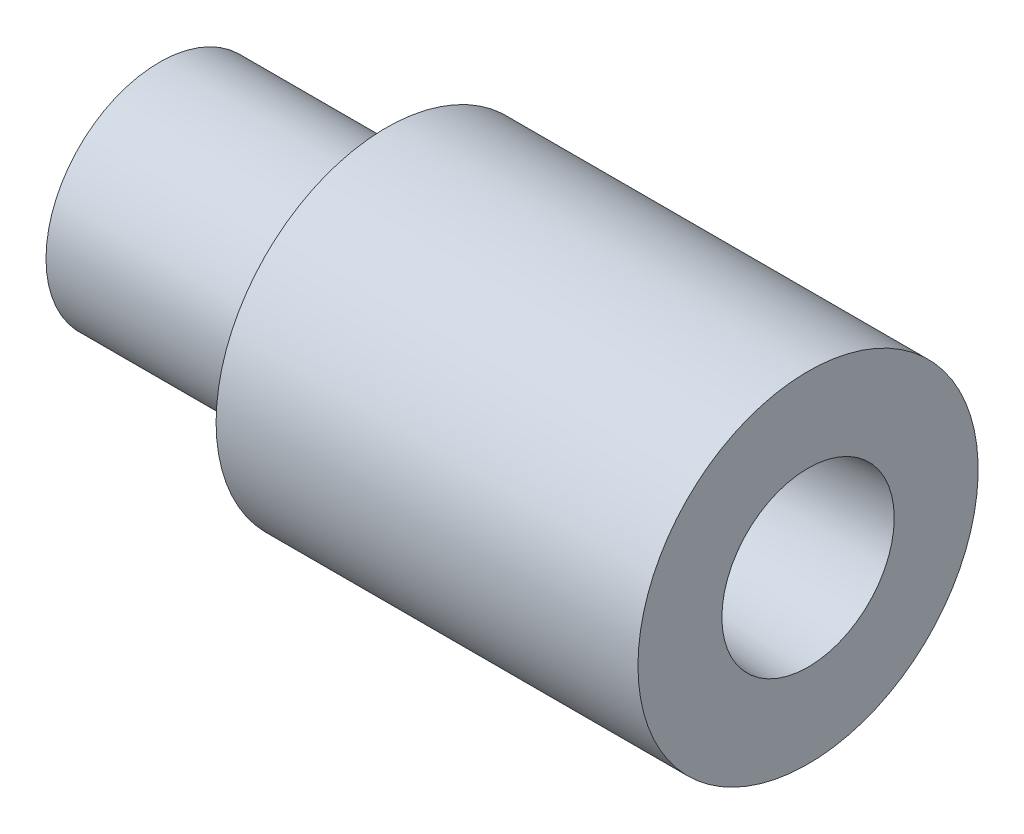
SolidWorks part; units mm, degrees
ref_plane "Front Plane" through (0, 0, 0) normal (0, 0, 1) x (1, 0, 0)
ref_plane "Top Plane" through (0, 0, 0) normal (0, 1, 0) x (1, 0, 0)
ref_plane "Right Plane" through (0, 0, 0) normal (1, 0, 0) x (0, 0, -1)
sketch "Sketch1" plane through (0, 0, 0) normal (0, 1, 0) x (1, 0, 0)
  line L0 (0, 0) -> (0, 2.286) construction
  line L1 (0, 2.286) -> (0, 6.35)
  line L2 (12.7, 9.525) -> (36.3237, 9.525)
  line L3 (36.3237, 9.525) -> (36.3237, 4.826)
  line L4 (36.3237, 4.826) -> (0, 2.286)
  line L5 (0, 0) -> (36.3237, 0) construction
  line L6 (36.3237, 0) -> (36.3237, 4.826) construction
  line L8 (12.7, 6.35) -> (12.7, 9.525)
  line L12 (0, 6.35) -> (12.7, 6.35)
  dimension "D1" = 2.286
  dimension "D2" = 4.826
  dimension "D3" = 4
  dimension "D4" = 9.525
  dimension "D5" = 6.35
  dimension "D6" = 12.7
revolve "Revolve1" add sketch "Sketch1" angle 360 about L5
equation "\"z\" = 8\t\t\t\t'number of blades"
equation "\"de\" = 0.43in\t\t\t'entrance eye diameter"
equation "\"de_length\" = 10mm\t\t'entrance eye consistent length"
equation "\"d_exit\" = 0.18in \t\t'throat aka d1"
equation "\"d2\" = 2.1in \t\t\t'outer diameter of the impeller"
equation "\"b2\" = .2in\t\t\t'tip height from disc surface at d2; slightly higher than d_exit"
equation "\"b1\" = \"b2\" + (\"d2\"/2 - \"de\"/2)*tan(\"theta\") \t\t\t'tip height from disc surface at inlet eye"
equation "\"theta\" = 12\t\t\t'angle of blades from inner to outer "
equation "\"ae\" = 3.14*(\"de\"^2)/4\t\t'entrance eye area'"
equation "\"ce\" = 3.14*\"de\"\t\t'entrance eye circumference"
equation "\"av_ratio\" = .325\t\t'ratio of av/ae at N_s of 470, range is .275 to .375, .325 ideal. High ratio means bigger area means smaller blades"
equation "\"av\" = \"ae\"*\"av_ratio\"\t\t'area between just two blades"
equation "\"s_open\" = \"av\"/\"b1\"\t\t'width of open area"
equation "\"s\"=\"ce\" - \"z\"*\"s_open\""
equation "\"min blade thickness\" = .15in"
equation "\"bearing OD\" = 30mm"
equation "\"bearing ID\"= 10mm"
equation "\"bearing depth\"= 9mm"
equation "\"bearing outer race thickness\"= 1mm"
equation "\"bearing inner race thickness\"= 1mm"
equation "\"bearing bore\" = \"bearing depth\" + 1mm"
equation "\"lower seal OD\" = .917in\t\t'this is https://www.mcmaster.com/#9281k121/=174001b"
equation "\"lower seal ID\"= .375in"
equation "\"lower seal depth\" = .625in + .218in"
equation "\"lower seal bore\" = \"lower seal depth\" + 1mm"
equation "\"upper seal OD\" = 1.125in\t'this is https://www.mcmaster.com/#5154t33/=173zuau, needs to be visually inspected before machining!"
equation "\"upper seal ID\"= 0.625in"
equation "\"upper seal depth\"= .25in\t'aka height; these values need to be confirmed by inspection!! We may want to compress the height."
equation "\"upper seal bore\" = \"upper seal depth\" + 1mm"
equation "\"big o-ring thickness\" = .139in"
equation "\"big o-ring OD\" = 2.734in"
equation "\"big o-ring ID\" = 3.012in"
equation "\"big o-ring groove depth\" = \"big o-ring thickness\"*4/5"
equation "\"impeller center height\" = \"impeller base thickness\" + \"b1\"\t'impeller height at de"
equation "\"impeller outer height\" = \"impeller base thickness\" + \"b2\"\t'impeller height at de"
equation "\"impeller upper clearance\"= .5mm"
equation "\"impeller horizontal clearance\"= (\"d2\"*1.15 - \"d2\")/2 \t\t'clearance based on D2-D3 ratio for circular volute, ranges 1.15 to 1.2"
equation "\"impeller bottom clearance\"= .5mm"
equation "\"impeller base thickness\"= 2mm"
equation "\"impeller dowel diameter\" = 2mm"
equation "\"impeller bolt head diameter\" = \"m4 head bore diameter\""
equation "\"impeller bolt head depth\" = 4mm"
equation "\"impeller bolt stop depth\" = 3mm"
equation "\"impeller bolt bore\" = \"m4 clearance\""
equation "\"impeller shaft bore depth\" = 12mm"
equation "\"impeller shaft bore\" = 8mm"
equation "\"impeller boss depth\" = \"impeller shaft bore depth\"+\"impeller bolt stop depth\"+\"impeller bolt head depth\"-\"impeller base thickness\""
equation "\"impeller boss diameter\" = \"upper seal ID\""
equation "\"impeller dowel length\" = 2mm*2 + \"impeller shaft bore\""
equation "\"coupler motor shaft hole ID\"= 8mm"
equation "\"coupler OD\"= 17mm"
equation "\"coupler length\"= 25mm"
equation "\"motor OD\" = 64mm"
equation "\"motor shaft diameter\"= 8mm"
equation "\"motor shaft pride\"= 32mm"
equation "\"motor to bearing plate distance\" = \"motor shaft pride\" + 2mm +\"coupler length\"/2"
equation "\"square plate bolt bore\" = \"m8 clearance\""
equation "\"square plate bolt head diameter\" = 13.5mm"
equation "\"square plate bolt head depth\" = 8mm"
equation "\"square plate bolt pattern diameter\"= 3.5in"
equation "\"motor mount center bore\"= \"coupler OD\"+ 4mm"
equation "\"motor mount post radius\"= ( 3 * \"square plate bolt bore\" ) / 2"
equation "\"motor mount m4 screw hole diameter\"= 4mm"
equation "\"motor mount m4 head diameter\"= 7.25mm"
equation "\"motor mount m4 head depth\"= 4mm"
equation "\"motor mount m4 pattern diamater\" = 30mm"
equation "\"motor mount plate thickness\"= 8mm + \"motor mount m4 head depth\""
equation "\"bearing plate stop ID\" = \"bearing OD\" - 4mm"
equation "\"bearing plate stop depth\" = 3mm"
equation "\"bearing plate thickness\" = \"bearing bore\" + \"bearing plate stop depth\" + \"shaft bearing stop length\""
equation "\"lower seal plate lip depth\" = 2mm"
equation "\"lower seal plate lip ID\" = \"lower seal OD\" - 3mm"
equation "\"lower seal plate thickness\" = \"lower seal plate lip depth\" + \"lower seal bore\""
equation "\"shaft coupler section diameter\" = 8mm"
equation "\"shaft coupler section length\" = \"motor to bearing plate distance\" - \"motor shaft pride\" - 2mm"
equation "\"shaft bearing section diameter\" = \"bearing ID\""
equation "\"shaft bearing section length\" = \"bearing plate stop depth\" + \"bearing depth\""
equation "\"shaft bearing stop diameter\" = \"bearing ID\" + 4mm"
equation "\"shaft bearing stop length\" = 3mm"
equation "\"shaft lower seal section diameter\" = \"lower seal ID\""
equation "\"shaft lower seal section length\" = \"lower seal plate thickness\" + 1mm"
equation "\"shaft impeller section diameter\" = \"impeller shaft bore\""
equation "\"shaft impeller section length\" = \"upper seal plate thickness\" + \"upper seal plate riser\" + \"impeller bottom clearance\" + \"impeller base thickness\" - \"impeller bolt head depth\" - \"impeller bolt stop depth\""
equation "\"upper seal plate thickness\" = \"upper seal plate pressure hole diameter\"+10mm"
equation "\"upper seal plate lip ID\" = \"upper seal OD\" - 3mm"
equation "\"upper seal plate riser\" = 6.59mm \t\t'this number needs to be read from the housing file"
equation "\"upper seal plate pressure hole diameter\" = .125in\t'this is 1/8 drill "
equation "\"upper seal plate pressure tap diameter\" = .328125in \t'this is 21/64 drill for a 1/8 ANPT tap"
equation "\"upper seal plate pressure tap grip\" = 5mm\t\t'this is the area around the tap so it doesn't crack"
equation "\"upper seal plate pressure tap depth\" = 12"
equation "\"impeller cavity center height\"= \"impeller bottom clearance\" + \"impeller upper clearance\" + \"impeller center height\""
equation "\"impeller cavity diameter\"= 2 * \"impeller horizontal clearance\" + \"d2\" \t\t\t\t\t\t\t\t\t'called D3 analytically"
equation "\"impeller cavity outer height\"= \"impeller bottom clearance\" + \"impeller upper clearance\" + \"impeller base thickness\" + \"b2\" \t\t'this is height at impeller diameter d2, not at d3"
equation "\"impeller housing thickness\"= \"impeller housing exit threaded diameter\" + 2*\"impeller housing outlet grip\""
equation "\"impeller housing diameter\" = \"square plate bolt pattern diameter\" + 2*\"motor mount post radius\""
equation "\"impeller housing bolt count\" = 8"
equation "\"impeller housing bolt diameter\" = \"m6 clearance\""
equation "\"impeller housing bolt pattern diameter\" = 3.5in"
equation "\"impeller housing threaded inlet diameter\" = 0.515625in \t'this is the 33/64 drill size for 9/16-18 fitting, expecting swagelok SS-8FK0-1-6STH fitting"
equation "\"impeller housing threaded inlet depth\"= 10mm"
equation "\"impeller housing exit threaded diameter\"= 0.515625in \t\t'this is the 33/64 drill size for 9/16-18 fitting, expecting swagelok SS-8FK0-1-6STH fitting"
equation "\"impeller housing exit threaded depth\"= 10mm"
equation "\"impeller housing diffuser conical angle\"=10"
equation "\"impeller housing diffuser tangent angle\"=5"
equation "\"impeller housing diffuser final diameter\" = .38in\t\t'aka d2'"
equation "\"impeller housing outlet grip\" = 5mm"
equation "\"end mill size\" = 0.375in\t'for 3/8 endmill"
equation "\"m4 clearance\" = 0.171875in \t'this is 11/64 bit for 4.36mm"
equation "\"m4 tap\" = 0.125in\t\t'this is 1/8 bit for 3.17mm"
equation "\"m4 head bore diameter\" = 7.5mm"
equation "\"m4 head bore depth\" = 5mm\t'actual is ~4mm"
equation "\"m6 clearance\" = 0.234375in\t'this is 15/64 bit = 5.95mm, could use 6mm bit, B bit for 6.04mm or 1/4 bit for 6.35mm"
equation "\"m6 tap\" = 5mm\t\t\t'5mm is appropriate, could use 13/64 or #5,6,7"
equation "\"m6 head bore diameter\" = 11mm\t\t"
equation "\"m6 head bore depth\" = 7mm\t'actual is 6mm"
equation "\"m8 clearance\" = 0.3125in\t'this is 5/16in for 7.93mm, could use 8mm, O,P, or 21/64"
equation "\"m8 tap\" = 0.265625in\t\t'this is 17/64 for 6.746875mm"
equation "\"m8 head bore diameter\" = 14mm"
equation "\"m8 head bore depth\" = 9mm\t'actual is 8mm"
equation "\"D1@Sketch1\"=\"d_exit\"/2"
equation "\"D2@Sketch1\"=\"impeller housing diffuser final diameter\"/2"
equation "\"diffuser cartridge OD\" =.75in"
equation "\"D4@Sketch1\"=\"diffuser cartridge OD\"/2"
